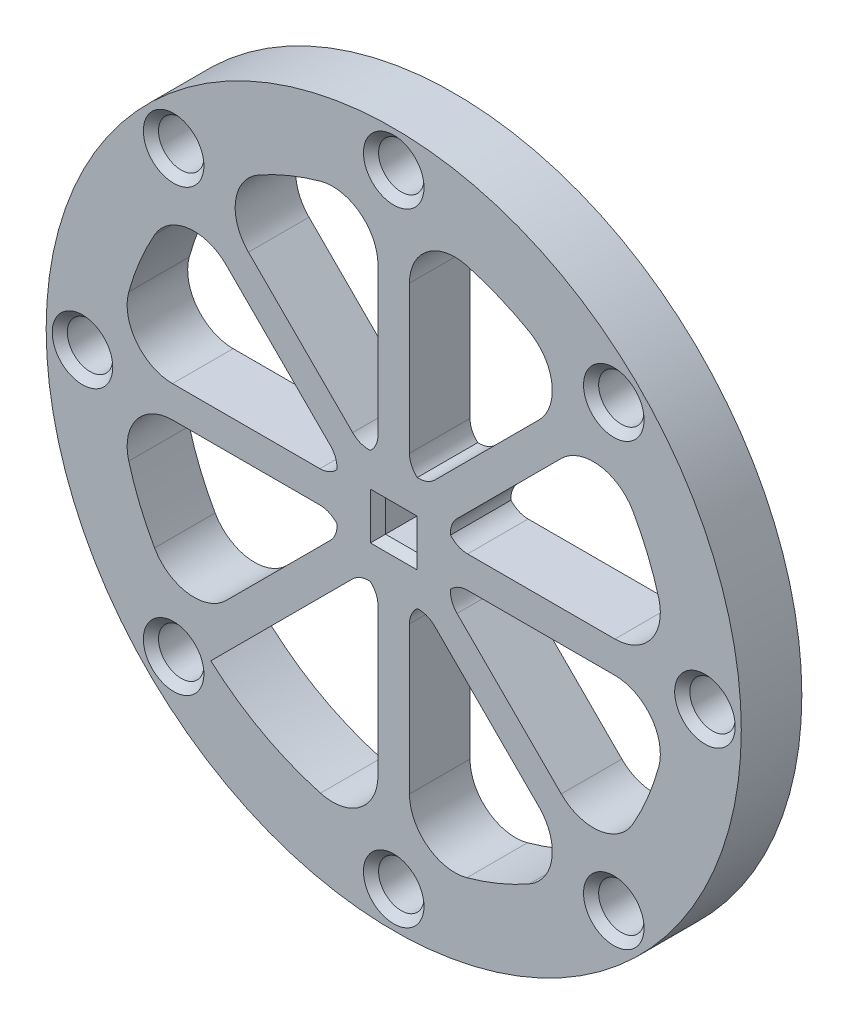
SolidWorks part; units mm, degrees
ref_plane "Front Plane" through (0, 0, 0) normal (0, 0, 1) x (1, 0, 0)
ref_plane "Top Plane" through (0, 0, 0) normal (0, 1, 0) x (1, 0, 0)
ref_plane "Right Plane" through (0, 0, 0) normal (1, 0, 0) x (0, 0, -1)
sketch "Sketch1" plane through (0, 0, 0) normal (0, 0, 1) x (1, 0, 0)
  line L0 (-1.651, 6.1316) -> (-1.651, 28.7817)
  line L1 (1.651, -1.651) -> (-1.651, -1.651)
  line L2 (1.651, -1.651) -> (1.651, 1.651)
  line L3 (1.651, 1.651) -> (-1.651, 1.651)
  line L4 (-1.651, -1.651) -> (-1.651, 1.651)
  line L5 (1.651, -1.651) -> (-1.651, 1.651) construction
  line L6 (1.651, 1.651) -> (-1.651, -1.651) construction
  line L7 (1.651, 6.1316) -> (1.651, 28.7817)
  line L8 (3.1683, 5.5031) -> (19.1843, 21.5192)
  line L9 (5.5031, 3.1683) -> (21.5192, 19.1843)
  line L10 (6.1316, 1.651) -> (28.7817, 1.651)
  line L11 (6.1316, -1.651) -> (28.7817, -1.651)
  line L12 (5.5031, -3.1683) -> (21.5192, -19.1843)
  line L13 (3.1683, -5.5031) -> (19.1843, -21.5192)
  line L14 (1.651, -6.1316) -> (1.651, -28.7817)
  line L15 (-1.651, -6.1316) -> (-1.651, -28.7817)
  line L16 (-3.1683, -5.5031) -> (-19.1843, -21.5192)
  line L17 (-5.5031, -3.1683) -> (-21.5192, -19.1843)
  line L18 (-6.1316, -1.651) -> (-28.7817, -1.651)
  line L19 (-6.1316, 1.651) -> (-28.7817, 1.651)
  line L20 (-5.5031, 3.1683) -> (-21.5192, 19.1843)
  line L21 (-3.1683, 5.5031) -> (-19.1843, 21.5192)
  line L22 (0, 0) -> (0, 32.639) construction
  circle A0 centre (0, 0) radius 36.449
  circle A1 centre (0, 0) radius 28.829
  circle A2 centre (0, 0) radius 6.35
  circle A3 centre (0, 32.639) radius 2.3812
  circle A4 centre (23.0793, 23.0793) radius 2.3812
  circle A5 centre (32.639, 0) radius 2.3812
  circle A6 centre (23.0793, -23.0793) radius 2.3813
  circle A11 centre (0, -32.639) radius 2.3812
  circle A12 centre (-23.0793, -23.0793) radius 2.3812
  circle A13 centre (-32.639, 0) radius 2.3812
  circle A14 centre (-23.0793, 23.0793) radius 2.3812
  dimension "D1" = 72.898
  dimension "D2" = 57.658
  dimension "D4" = 12.7
  dimension "D6" = 4.7625
  dimension "D3" = 3.302
  dimension "D7" = 32.639
  dimension "D5" = 8
extrude "Boss-Extrude1" add sketch "Sketch1" along normal blind 6.35
fillet "Fillet1" radius 4.7625 15 edges at (19.1843, -21.5192, 3.175) (21.5192, -19.1843, 3.175) (28.7817, -1.651, 3.175) (28.7817, 1.651, 3.175) (21.5192, 19.1843, 3.175) (19.1843, 21.5192, 3.175) (1.651, 28.7817, 3.175) (-1.651, 28.7817, 3.175) (-1.651, -28.7817, 3.175) (-28.7817, -1.651, 3.175) (-21.5192, 19.1843, 3.175) (-28.7817, 1.651, 3.175) (-21.5192, -19.1843, 3.175) (1.651, -28.7817, 3.175) (-19.1843, 21.5192, 3.175)
fillet "Fillet2" radius 2.3813 16 edges at (6.1316, -1.651, 3.175) (5.5031, -3.1683, 3.175) (3.1683, 5.5031, 3.175) (6.1316, 1.651, 3.175) (1.651, 6.1316, 3.175) (5.5031, 3.1683, 3.175) (-1.651, 6.1316, 3.175) (3.1683, -5.5031, 3.175) (-3.1683, 5.5031, 3.175) (-6.1316, 1.651, 3.175) (-5.5031, 3.1683, 3.175) (-5.5031, -3.1683, 3.175) (-6.1316, -1.651, 3.175) (-1.651, -6.1316, 3.175) (-3.1683, -5.5031, 3.175) (1.651, -6.1316, 3.175)
chamfer "Chamfer1" distance 0.7937 angle 45 24 edges at (2.3812, 32.639, 6.35) (2.3812, 32.639, 0) (25.4605, -23.0793, 6.35) (25.4605, -23.0793, 0) (35.0203, 0, 6.35) (35.0203, 0, 0) (0, 1.651, 0) (0, 1.651, 6.35) (-1.651, 0, 0) (-1.651, 0, 6.35) (0, -1.651, 0) (0, -1.651, 6.35) (1.651, 0, 0) (1.651, 0, 6.35) (25.4605, 23.0793, 6.35) (25.4605, 23.0793, 0) (-20.698, 23.0793, 6.35) (-20.698, 23.0793, 0) (-30.2578, 0, 6.35) (-30.2578, 0, 0) (-20.698, -23.0793, 6.35) (-20.698, -23.0793, 0) (2.3812, -32.639, 6.35) (2.3812, -32.639, 0)
equation "\"D2@Sketch1\"=\"D1@Sketch1\"-.6"
equation "\"D7@Sketch1\"=(\"D1@Sketch1\"+\"D2@Sketch1\")/4"
